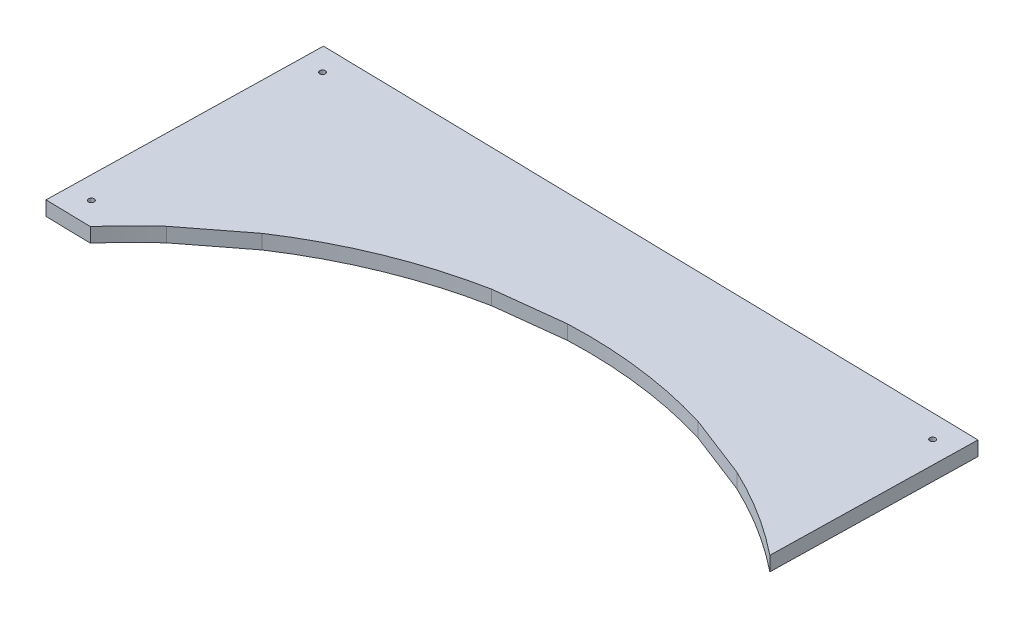
SolidWorks part; units mm, degrees
material "Balsa"
ref_plane "Front Plane" through (0, 0, 0) normal (0, 0, 1) x (1, 0, 0)
ref_plane "Top Plane" through (0, 0, 0) normal (0, 1, 0) x (1, 0, 0)
ref_plane "Right Plane" through (0, 0, 0) normal (1, 0, 0) x (0, 0, -1)
sketch "Sketch1" plane through (0, 0, 0) normal (0, 1, 0) x (1, 0, 0)
  line L0 (-12.8843, 57.5899) -> (-32.8801, 58.0016)
  line L5 (-32.8801, 58.0016) -> (-30.4097, 177.9762)
  line L6 (-30.4097, 177.9762) -> (264.5278, 171.9031)
  line L7 (264.5278, 171.9031) -> (262.6746, 81.9031)
  line L17 (3.8471, 74.5464) -> (27.5977, 92.8811)
  line L18 (99.6149, 122.2056) -> (129.6149, 125.6852)
  line L19 (195.598, 117.2478) -> (223.6208, 106.3964)
  arc A0 (-12.8843, 57.5899) -> (3.8471, 74.5464) centre (137.592, -74.1557) cw
  arc A1 (27.5977, 92.8811) -> (99.6149, 122.2056) centre (137.592, -74.1557) cw
  arc A2 (129.6149, 125.6852) -> (195.598, 117.2478) centre (137.592, -74.1557) cw
  arc A3 (223.6208, 106.3964) -> (262.6746, 81.9031) centre (137.592, -74.1557) cw
  circle A4 centre (-20.6177, 167.7724) radius 1.25
  circle A5 centre (-22.6763, 67.7936) radius 1.25
  circle A6 centre (254.3241, 162.1111) radius 1.25
  point P17 (0, 0)
  dimension "D5" = 200
  dimension "D8" = 2.5
  dimension "D11" = 2.5
  dimension "D14" = 2.5
  dimension "D1" = 295
  dimension "D2" = 20
  dimension "D3" = 120
  dimension "D4" = 90
  dimension "D6" = 10
  dimension "D7" = 10
  dimension "D9" = 10
  dimension "D10" = 10
  dimension "D12" = 10
  dimension "D13" = 10
extrude "Boss-Extrude1" add sketch "Sketch1" along normal blind 6.35
